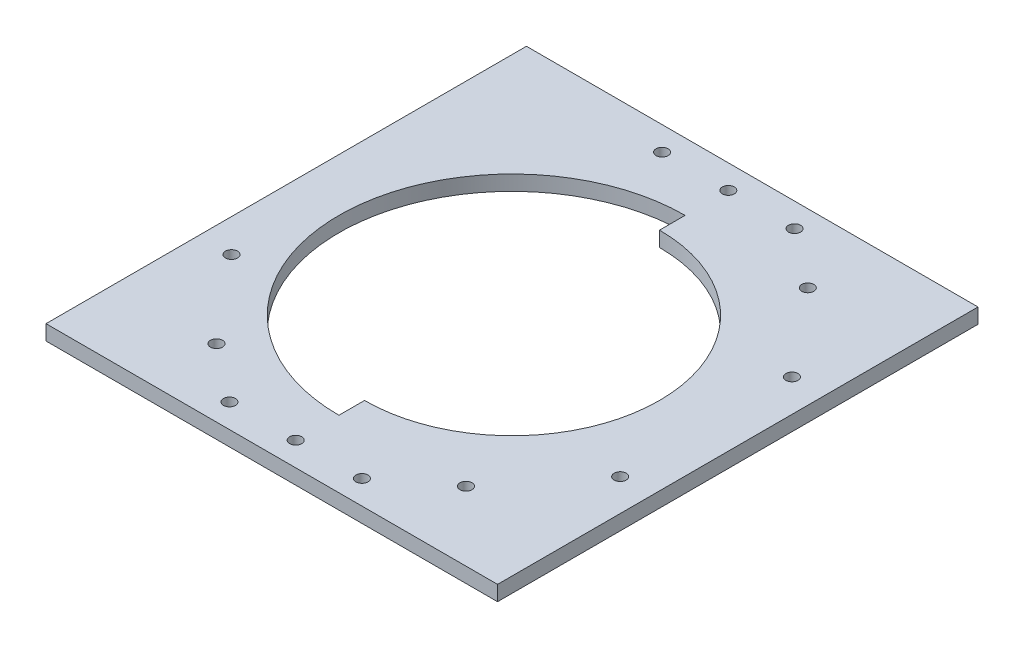
SolidWorks part; units mm, degrees
ref_plane "Front Plane" through (0, 0, 0) normal (0, 0, 1) x (1, 0, 0)
ref_plane "Top Plane" through (0, 0, 0) normal (0, 1, 0) x (1, 0, 0)
ref_plane "Right Plane" through (0, 0, 0) normal (1, 0, 0) x (0, 0, -1)
sketch "Sketch1" plane through (0, 0, 0) normal (0, 1, 0) x (1, 0, 0)
  line L0 (-266.663, 35.6247) -> (-120.5123, 35.6247) construction
  line L1 (-341.663, 115.4247) -> (-191.663, 115.4247)
  line L2 (-341.663, 115.4247) -> (-341.663, -44.1753)
  line L3 (-341.663, -44.1753) -> (-191.663, -44.1753)
  line L4 (-191.663, 115.4247) -> (-191.663, -44.1753)
  line L5 (-341.663, 115.4247) -> (-191.663, -44.1753) construction
  line L6 (-341.663, -44.1753) -> (-191.663, 115.4247) construction
  line L7 (-288.663, 107.4807) -> (-244.663, 107.4807) construction
  line L10 (-266.663, -88.6648) -> (-266.663, -97.3376) construction
  circle A0 centre (-266.663, 35.6247) radius 49
  circle A1 centre (-288.663, 107.4807) radius 2
  circle A3 centre (-244.663, 107.4807) radius 2
  circle A4 centre (-244.663, -36.2312) radius 2
  circle A5 centre (-266.663, -36.2312) radius 2
  circle A6 centre (-288.663, -36.2312) radius 2
  circle A7 centre (-266.663, 107.4807) radius 2
  point P0 (-266.663, 35.6247)
  dimension "D3" = 98
  dimension "D4" = 4
  dimension "D5" = 4
  dimension "D6" = 4
  dimension "D1" = 159.6
  dimension "D2" = 150
  dimension "D7" = 44
extrude "Boss-Extrude1" add sketch "Sketch1" along normal blind 5
sketch "Sketch2" plane through (0, 5, 0) normal (0, 1, 0) x (1, 0, 0)
  line L0 (-341.663, 115.4247) -> (-191.663, -44.1753) construction
  line L1 (-341.663, 115.4247) -> (-341.663, -44.1753) construction
  line L2 (-341.663, -44.1753) -> (-191.663, -44.1753) construction
  circle A0 centre (-330.7262, 6.5062) radius 2
  circle A1 centre (-307.5841, -21.6243) radius 2
  circle A4 centre (-225.4275, 92.6477) radius 2
  circle A5 centre (-202.4405, 64.3904) radius 2
  circle A6 centre (-225.1346, -21.1853) radius 2
  circle A9 centre (-202.2933, 7.1899) radius 2
extrude "Cut-Extrude2" cut sketch "Sketch2" against normal through all both and the other way through all
sketch "Sketch3" plane through (0, 5, 0) normal (0, 1, 0) x (1, 0, 0)
  line L0 (-266.663, 93.1247) -> (-266.663, -21.8753)
  arc A1 (-266.663, 93.1247) -> (-266.663, -21.8753) centre (-266.663, 35.6247) ccw
extrude "Cut-Extrude3" cut sketch "Sketch3" against normal through all both and the other way through all
